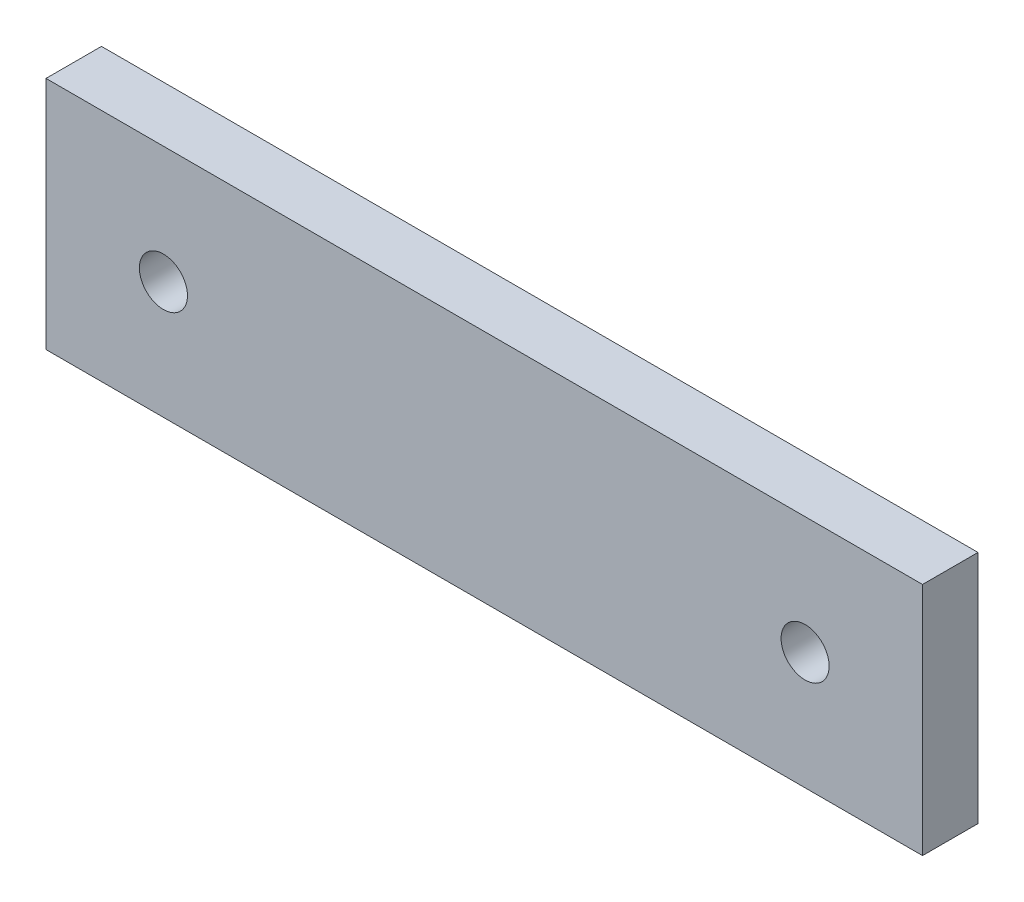
SolidWorks part; units mm, degrees
ref_plane "Front Plane" through (0, 0, 0) normal (0, 0, 1) x (1, 0, 0)
ref_plane "Top Plane" through (0, 0, 0) normal (0, 1, 0) x (1, 0, 0)
ref_plane "Right Plane" through (0, 0, 0) normal (1, 0, 0) x (0, 0, -1)
sketch "Sketch1" plane through (0, 0, 0) normal (0, 0, 1) x (1, 0, 0)
  line L0 (-34.7, 0) -> (34.7, 0) construction
  line L1 (-47.4, -12.7) -> (47.4, -12.7)
  line L2 (-47.4, -12.7) -> (-47.4, 12.7)
  line L3 (-47.4, 12.7) -> (47.4, 12.7)
  line L4 (47.4, -12.7) -> (47.4, 12.7)
  line L5 (-47.4, -12.7) -> (47.4, 12.7) construction
  line L6 (-47.4, 12.7) -> (47.4, -12.7) construction
  circle A0 centre (34.7, 0) radius 2.6
  circle A1 centre (-34.7, 0) radius 2.6
  point P0 (0, 0)
  point P9 (0, 0)
  dimension "D1" = 94.8
  dimension "D4" = 5.2
  dimension "D2" = 12.7
  dimension "D3" = 25.4
extrude "Boss-Extrude1" add sketch "Sketch1" along normal blind 6
